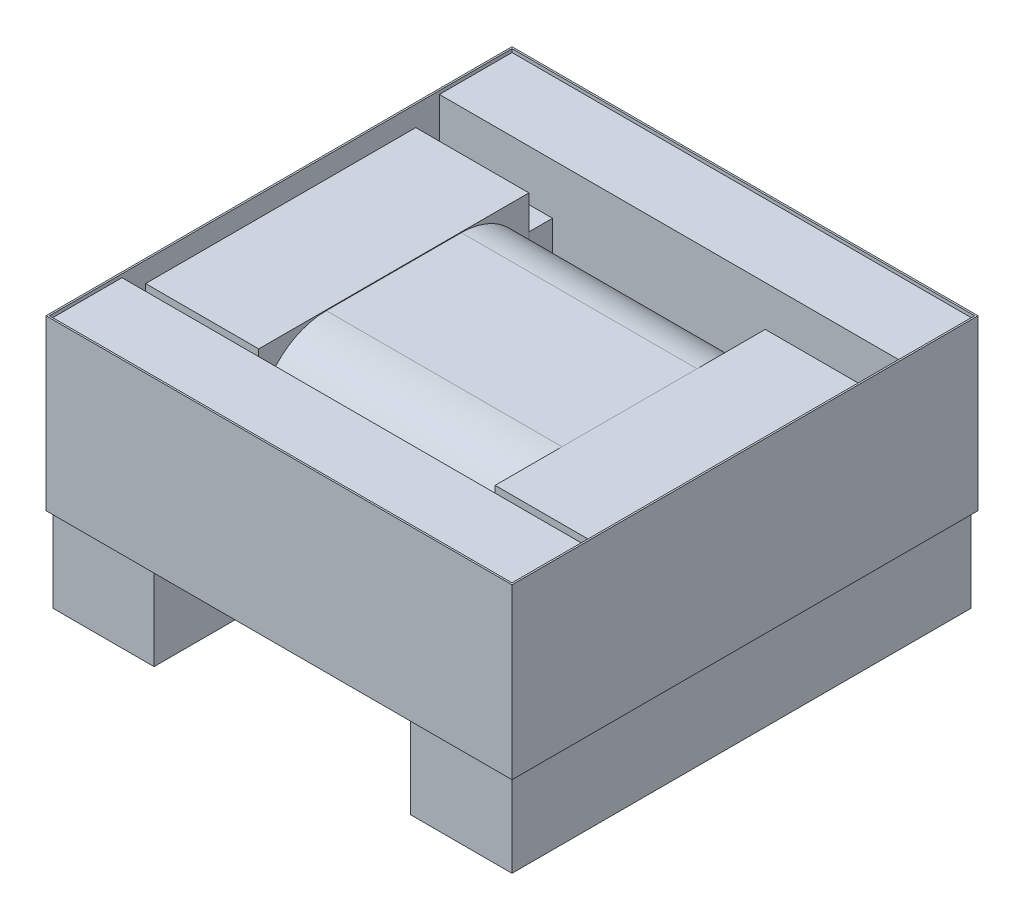
SolidWorks part; units mm, degrees
ref_plane "Plano frontal" through (0, 0, 0) normal (0, 0, 1) x (1, 0, 0)
ref_plane "Plano superior" through (0, 0, 0) normal (0, 1, 0) x (1, 0, 0)
ref_plane "Plano direito" through (0, 0, 0) normal (1, 0, 0) x (0, 0, -1)
sketch "Esboço1" plane through (0, 0, 0) normal (0, 1, 0) x (1, 0, 0)
  line L1 (-6.9, -6.9) -> (6.9, -6.9)
  line L2 (-6.9, -6.9) -> (-6.9, 6.9)
  line L3 (-6.9, 6.9) -> (6.9, 6.9)
  line L4 (6.9, -6.9) -> (6.9, 6.9)
  line L5 (-6.9, -6.9) -> (6.9, 6.9) construction
  line L6 (-6.9, 6.9) -> (6.9, -6.9) construction
  point P0 (0, 0)
  dimension "D1" = 13.8
  dimension "D2" = 13.8
extrude "Ressalto-extrusão1" add sketch "Esboço1" along normal blind 5
sketch "Esboço3" plane through (0, 0, 0) normal (0, -1, 0) x (1, 0, 0)
  line L0 (-6.9, -6.9) -> (-6.9, 6.9) construction
  line L1 (-6.8, 6.8) -> (-3.8, 6.8)
  line L2 (-6.8, 6.8) -> (-6.8, -6.8)
  line L3 (-6.8, -6.8) -> (-3.8, -6.8)
  line L4 (-3.8, 6.8) -> (-3.8, -6.8)
  line L5 (3.8, 6.8) -> (6.8, 6.8)
  line L6 (3.8, 6.8) -> (3.8, -6.8)
  line L7 (3.8, -6.8) -> (6.8, -6.8)
  line L8 (6.8, 6.8) -> (6.8, -6.8)
  line L9 (-6.9, 6.9) -> (6.9, 6.9) construction
  line L10 (6.9, -6.9) -> (-6.9, -6.9) construction
  line L11 (6.9, 6.9) -> (6.9, -6.9) construction
  dimension "D1" = 0.1
  dimension "D2" = 0.1
  dimension "D3" = 0.1
  dimension "D4" = 0.1
  dimension "D5" = 0.1
  dimension "D6" = 0.1
  dimension "D7" = 3
  dimension "D8" = 3
extrude "Ressalto-extrusão3" add sketch "Esboço3" along normal blind 2.5
sketch "Esboço4" plane through (0, 5, 0) normal (0, 1, 0) x (1, 0, 0)
  line L0 (-6.9, 6.9) -> (-6.9, -6.9) construction
  line L1 (-6.85, -6.85) -> (6.85, -6.85)
  line L2 (-6.85, -6.85) -> (-6.85, 6.85)
  line L3 (-6.85, 6.85) -> (6.85, 6.85)
  line L4 (6.85, -6.85) -> (6.85, 6.85)
  line L5 (-6.85, -6.85) -> (6.85, 6.85) construction
  line L6 (-6.85, 6.85) -> (6.85, -6.85) construction
  line L7 (6.9, 6.9) -> (-6.9, 6.9) construction
  point P0 (0, 0)
  dimension "D1" = 0.05
  dimension "D2" = 0.05
extrude "Corte-extrusão1" cut sketch "Esboço4" against normal blind 0.1
sketch "Esboço5" plane through (0, 4.9, 0) normal (0, 1, 0) x (1, 0, 0)
  line L0 (-6.85, 6.85) -> (-6.85, -6.85) construction
  line L1 (-6.85, 4.7) -> (6.85, 4.7)
  line L2 (-6.85, 4.7) -> (-6.85, -4.7)
  line L3 (-6.85, -4.7) -> (6.85, -4.7)
  line L4 (6.85, 4.7) -> (6.85, -4.7)
  line L5 (6.85, -6.85) -> (6.85, 6.85) construction
  line L6 (6.9, 6.9) -> (-6.9, 6.9) construction
  line L7 (-6.9, -6.9) -> (6.9, -6.9) construction
  dimension "D1" = 2.2
  dimension "D2" = 2.2
extrude "Corte-extrusão2" cut sketch "Esboço5" against normal blind 0.5
sketch "Esboço6" plane through (0, 4.4, 0) normal (0, 1, 0) x (-1, 0, 0)
  line L0 (-6.85, 4.7) -> (-6.85, -4.7) construction
  line L1 (6.85, -4.7) -> (-6.85, -4.7)
  line L2 (6.85, -4.7) -> (6.85, -4)
  line L3 (6.85, -4) -> (-6.85, -4)
  line L4 (-6.85, -4.7) -> (-6.85, -4)
  line L5 (6.85, -6.85) -> (6.85, 6.85) construction
  line L6 (-6.85, 4.7) -> (6.85, 4.7)
  line L7 (-6.85, 4.7) -> (-6.85, 4)
  line L8 (-6.85, 4) -> (6.85, 4)
  line L9 (6.85, 4.7) -> (6.85, 4)
  dimension "D1" = 0.7
  dimension "D2" = 0.7
extrude "Corte-extrusão3" cut sketch "Esboço6" against normal blind 1
sketch "Esboço7" plane through (0, 3.4, 0) normal (0, 1, 0) x (1, 0, 0)
  line L0 (6.85, 4.7) -> (-6.85, 4.7) construction
  line L1 (-3.5, 4.7) -> (3.5, 4.7)
  line L2 (-3.5, 4.7) -> (-3.5, 4)
  line L3 (-3.5, 4) -> (3.5, 4)
  line L4 (3.5, 4.7) -> (3.5, 4)
  line L5 (-6.85, 4) -> (6.85, 4) construction
  line L6 (6.85, -4) -> (-6.85, -4) construction
  line L7 (-3.5, -4) -> (3.5, -4)
  line L8 (-3.5, -4) -> (-3.5, -4.7)
  line L9 (-3.5, -4.7) -> (3.5, -4.7)
  line L10 (3.5, -4) -> (3.5, -4.7)
  line L11 (-6.85, -4.7) -> (6.85, -4.7) construction
  dimension "D1" = 7
  dimension "D2" = 3.5
extrude "Corte-extrusão4" cut sketch "Esboço7" against normal blind 10
sketch "Esboço8" plane through (0, 4.4, 0) normal (0, 1, 0) x (1, 0, 0)
  line L0 (6.85, -4) -> (-6.85, -4) construction
  line L1 (-3.5, 4) -> (3.5, 4)
  line L2 (-3.5, 4) -> (-3.5, -4)
  line L3 (-3.5, -4) -> (3.5, -4)
  line L4 (3.5, 4) -> (3.5, -4)
  line L5 (6.85, -4) -> (3.5, -4) construction
extrude "Corte-extrusão5" cut sketch "Esboço8" against normal blind 0.02
fillet "Filete1" radius 2 2 edges at (0, 4.38, 4) (0, 4.38, -4)
